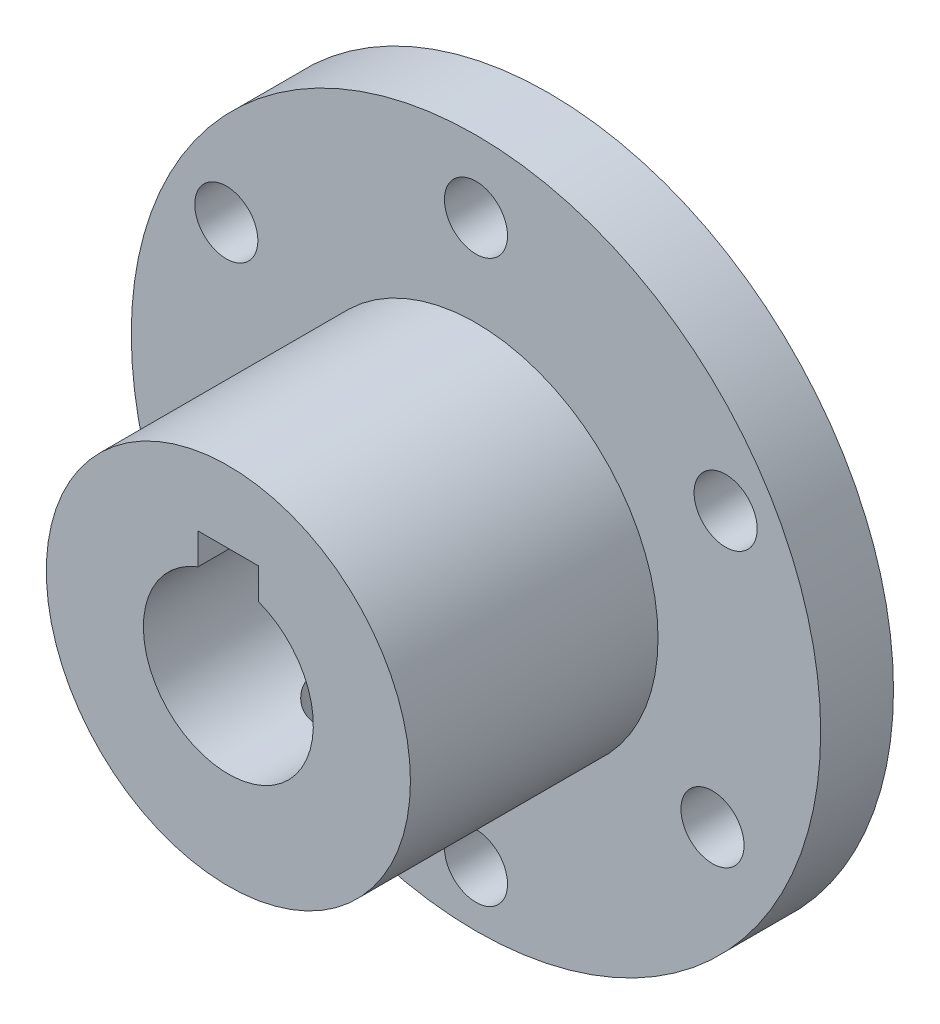
SolidWorks part; units mm, degrees
ref_plane "前视基准面" through (0, 0, 0) normal (0, 0, 1) x (1, 0, 0)
ref_plane "上视基准面" through (0, 0, 0) normal (0, 1, 0) x (1, 0, 0)
ref_plane "右视基准面" through (0, 0, 0) normal (1, 0, 0) x (0, 0, -1)
sketch "草图1" plane through (0, 0, 0) normal (0, 0, 1) x (1, 0, 0)
  circle A0 centre (0, 0) radius 7
  circle A1 centre (0, 0) radius 15
  dimension "D1" = 14
  dimension "D2" = 30
extrude "凸台-拉伸1" add sketch "草图1" along normal blind 20.4
sketch "草图2" plane through (0, 0, 0) normal (0, 0, -1) x (-1, 0, 0)
  circle A0 centre (0, 0) radius 28.4
  circle A1 centre (0, 0) radius 7
  dimension "D1" = 56.8
extrude "凸台-拉伸2" add sketch "草图2" along normal blind 6
sketch "草图3" plane through (0, 0, 0) normal (0, 0, 1) x (1, 0, 0)
  line L0 (0, 0) -> (36.1973, 0) construction
  line L1 (0, 0) -> (39.2724, -22.6739) construction
  circle A0 centre (0, 0) radius 23.75 construction
  circle A1 centre (0, 0) radius 22.5 construction
  circle A2 centre (0, -23.75) radius 2.6
  circle A3 centre (-20.5681, 11.875) radius 2.6
  circle A4 centre (20.5681, 11.875) radius 2.6
  circle A5 centre (19.4856, -11.25) radius 2.6
  circle A6 centre (-19.4856, -11.25) radius 2.6
  circle A7 centre (0, 22.5) radius 2.6
  dimension "D1" = 47.5
  dimension "D2" = 45
  dimension "D3" = 5.2
  dimension "D6" = 5.2
  dimension "D5" = 30
  dimension "D4" = 3
  dimension "D7" = 3
extrude "切除-拉伸1" cut sketch "草图3" against normal blind 6
sketch "草图4" plane through (0, 0, 20.4) normal (0, 0, 1) x (1, 0, 0)
  line L1 (2.5, 4.9) -> (-2.5, 4.9)
  line L2 (2.5, 4.9) -> (2.5, 9.1)
  line L3 (2.5, 9.1) -> (-2.5, 9.1)
  line L4 (-2.5, 4.9) -> (-2.5, 9.1)
  line L5 (2.5, 4.9) -> (-2.5, 9.1) construction
  line L6 (2.5, 9.1) -> (-2.5, 4.9) construction
  circle A0 centre (0, 0) radius 7 construction
  point P0 (0, 7)
  dimension "D1" = 5
  dimension "D2" = 4.2
extrude "切除-拉伸2" cut sketch "草图4" against normal blind 50
sketch "草图5" plane through (0, 0, 0) normal (0, 1, 0) x (1, 0, 0)
  line L0 (-15, -20.4) -> (15, -20.4) construction
  circle A0 centre (0, -10.2) radius 3
  dimension "D1" = 6
  dimension "D2" = 10.2
extrude "切除-拉伸3" cut sketch "草图5" against normal blind 20.4
